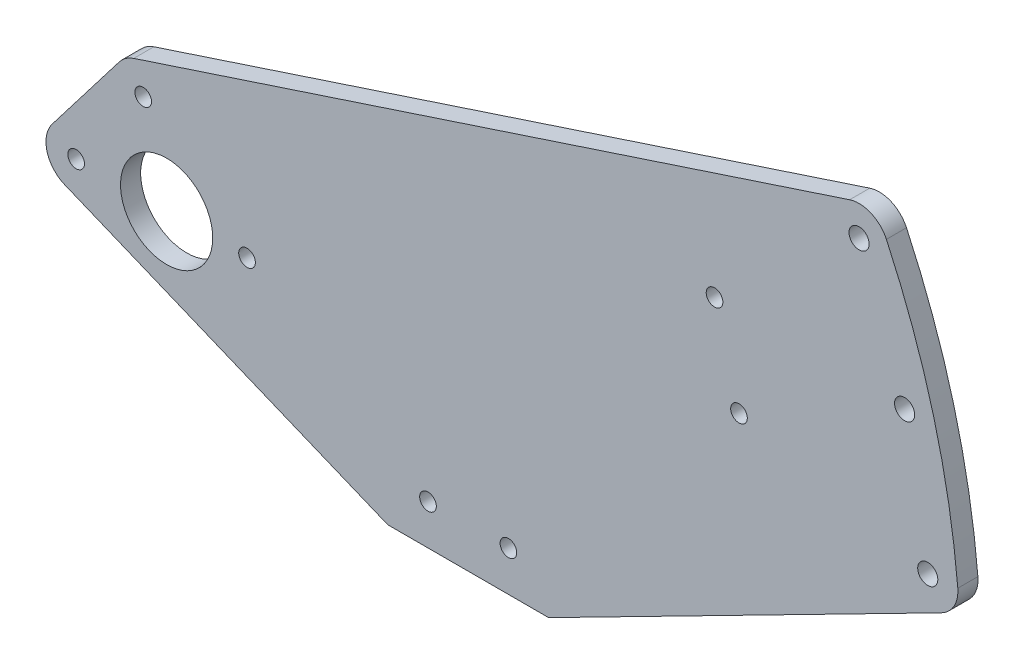
SolidWorks part; units mm, degrees
material "6061-T6 (SS)"
ref_plane "Front Plane" through (0, 0, 0) normal (0, 0, 1) x (1, 0, 0)
ref_plane "Top Plane" through (0, 0, 0) normal (0, 1, 0) x (1, 0, 0)
ref_plane "Right Plane" through (0, 0, 0) normal (1, 0, 0) x (0, 0, -1)
sketch "Sketch1" plane through (0, 0, 0) normal (0, 0, 1) x (1, 0, 0)
  line L0 (0, 0) -> (-28.575, 0) construction
  line L1 (0, 0) -> (-7.3958, 27.6013) construction
  line L2 (0, 0) -> (240.3818, 21.0307) construction
  line L3 (0, 0) -> (25.4, 0) construction
  line L4 (0, 0) -> (240.3818, 21.0307) construction
  line L5 (0, 0) -> (233.0779, 62.453) construction
  line L6 (-36.1317, 5.7985) -> (-14.9524, 33.3998)
  line L7 (-32.1995, -8.8084) -> (69.85, -50.8)
  line L8 (-10.3723, 36.6493) -> (215.7155, 111.0258)
  line L10 (0, 0) -> (0, -38.1) construction
  line L11 (0, -38.1) -> (233.0779, -38.1) construction
  line L12 (82.55, -38.1) -> (107.95, -38.1) construction
  line L13 (69.85, -50.8) -> (120.65, -50.8)
  line L14 (120.65, -50.8) -> (244.7133, 12.5476)
  line L15 (0, 0) -> (173.0444, 62.983) construction
  line L16 (0, 0) -> (180.7666, 35.1375) construction
  circle A0 centre (0, 0) radius 14.5542
  circle A1 centre (-28.575, 0) radius 2.6289
  circle A2 centre (-7.3958, 27.6013) radius 2.6289
  circle A3 centre (240.3818, 21.0307) radius 3.175
  circle A4 centre (233.0779, 62.453) radius 3.175
  circle A5 centre (218.6921, 101.9778) radius 3.175
  arc A7 (-32.1995, -8.8084) -> (-36.1317, 5.7985) centre (-28.575, 0) cw
  arc A8 (-10.3723, 36.6493) -> (-14.9524, 33.3998) centre (-7.3958, 27.6013) ccw
  arc A9 (227.3247, 106.0032) -> (215.7155, 111.0258) centre (218.6921, 101.9778) ccw
  arc A10 (227.3247, 106.0032) -> (249.8705, 21.8608) centre (0, 0) cw
  arc A11 (249.8705, 21.8608) -> (244.7133, 12.5476) centre (240.3818, 21.0307) cw
  circle A12 centre (82.55, -38.1) radius 2.6289
  circle A13 centre (107.95, -38.1) radius 2.6289
  circle A14 centre (25.4, 0) radius 2.6289
  circle A15 centre (173.0444, 62.983) radius 2.6289
  circle A16 centre (180.7666, 35.1375) radius 2.6289
  dimension "D1" = 29.1084
  dimension "D3" = 5.2578
  dimension "D6" = 5.2578
  dimension "D9" = 6.35
  dimension "D12" = 9.525
  dimension "D13" = 9.525
  dimension "D14" = 12.7
  dimension "D15" = 9.525
  dimension "D17" = 5.2578
  dimension "D18" = 5.2578
  dimension "D19" = 82.55
  dimension "D20" = 25.4
  dimension "D22" = 12.7
  dimension "D24" = 5.2578
  dimension "D27" = 5.2578
  dimension "D29" = 5.2578
  dimension "D2" = 28.575
  dimension "D4" = 75
  dimension "D5" = 28.575
  dimension "D7" = 5
  dimension "D8" = 241.3
  dimension "D11" = 10
  dimension "D16" = 38.1
  dimension "D21" = 12.7
  dimension "D23" = 25.4
  dimension "D25" = 15
  dimension "D26" = 184.15
  dimension "D28" = 6
  dimension "D30" = 184.15
  dimension "D10" = 3
extrude "Boss-Extrude1" add sketch "Sketch1" along normal blind 6.35
